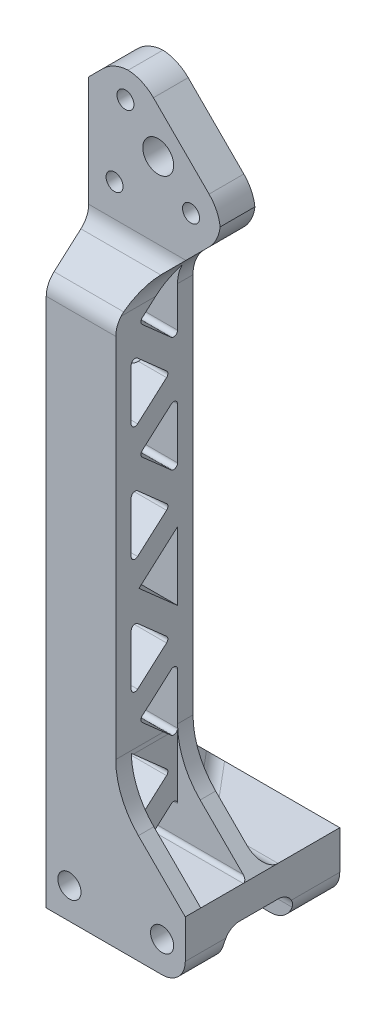
SolidWorks part; units mm, degrees
ref_plane "Front Plane" through (0, 0, 0) normal (0, 0, 1) x (1, 0, 0)
ref_plane "Top Plane" through (0, 0, 0) normal (0, 1, 0) x (1, 0, 0)
ref_plane "Right Plane" through (0, 0, 0) normal (1, 0, 0) x (0, 0, -1)
sketch "Sketch1" plane through (0, 0, 0) normal (0, 0, 1) x (1, 0, 0)
  line L0 (0, 90.435) -> (0, 0)
  line L1 (0, 0) -> (15, 0)
  line L2 (18, 3) -> (18, 8)
  line L3 (18, 8) -> (11.9289, 14.0711)
  line L4 (9, 21.1421) -> (9, 72.565)
  line L5 (9, 72.565) -> (9, 86) construction
  line L6 (3, 4) -> (15, 4) construction
  line L7 (0, 90.435) -> (3.3076, 93.7426)
  line L8 (3.3076, 93.7426) -> (6.9142, 93.7426)
  line L9 (6.9142, 93.7426) -> (17.0459, 83.6109)
  line L10 (17.0459, 83.6109) -> (17.0459, 80.6109)
  line L11 (17.0459, 80.6109) -> (9, 72.565)
  line L12 (4.7574, 90.2426) -> (9, 86) construction
  line L13 (9, 86) -> (13.2426, 81.7574) construction
  line L14 (9, 86) -> (3.3431, 80.3431) construction
  circle A0 centre (9, 86) radius 6 construction
  circle A1 centre (9, 86) radius 8 construction
  circle A2 centre (15, 4) radius 1.5
  circle A3 centre (3, 4) radius 1.5
  arc A4 (15, 0) -> (18, 3) centre (15, 3) ccw
  circle A5 centre (13.2426, 81.7574) radius 1.1
  circle A6 centre (3.3431, 80.3431) radius 1.1
  circle A7 centre (4.7574, 90.2426) radius 1.1
  circle A8 centre (9, 86) radius 2
  arc A9 (11.9289, 14.0711) -> (9, 21.1421) centre (19, 21.1421) cw
  point P16 (18, 0)
  point P30 (3.3431, 93.7426)
  point P31 (0, 90.2426)
  point P32 (17.0459, 83.6109)
  dimension "D7" = 3
  dimension "D8" = 3
  dimension "D11" = 12
  dimension "D12" = 16
  dimension "D17" = 2.2
  dimension "D21" = 4
  dimension "D24" = 10
  dimension "D1" = 18
  dimension "D2" = 8
  dimension "D3" = 12
  dimension "D4" = 4
  dimension "D5" = 3
  dimension "D6" = 135
  dimension "D9" = 9
  dimension "D10" = 82
  dimension "D13" = 45
  dimension "D14" = 90
  dimension "D15" = 90
  dimension "D16" = 3.5
  dimension "D18" = 3.5
  dimension "D19" = 3.5
  dimension "D20" = 45
  dimension "D22" = 4
  dimension "D23" = 3
extrude "Boss-Extrude1" add sketch "Sketch1" along normal mid plane 10
sketch "Sketch2" plane through (0, 0, 0) normal (-1, 0, 0) x (0, 0, 1)
  line L0 (-3, -952.5072) -> (-3, 49047.4928) construction
  line L1 (-2, -952.5072) -> (-2, 49047.4928) construction
  line L2 (3, 8) -> (-3, 8)
  line L3 (0, -952.5072) -> (0, 49047.4928) construction
  line L4 (2, -952.5072) -> (2, 49047.4928) construction
  line L5 (3, -952.2832) -> (3, 49047.7168) construction
  line L6 (5, 90.435) -> (5, 0) construction
  line L7 (-5, 90.435) -> (-5, 0) construction
  line L8 (-3, 8) -> (-3, 13.3)
  line L9 (-3, 13.3) -> (3, 8)
  line L10 (3, 12.0028) -> (-2, 16.4195)
  line L11 (-2, 16.4195) -> (3, 20.8361)
  line L12 (3, 20.8361) -> (3, 12.0028)
  line L13 (2, 23.9556) -> (-3, 28.3723)
  line L14 (-3, 28.3723) -> (-3, 19.539)
  line L15 (-3, 19.539) -> (2, 23.9556)
  line L16 (3, 35.7111) -> (3, 26.8778)
  line L17 (3, 26.8778) -> (-2, 31.2944)
  line L18 (-2, 31.2944) -> (3, 35.7111)
  line L19 (-3, 34.4139) -> (2, 38.8306)
  line L20 (2, 38.8306) -> (-3, 43.2473)
  line L21 (-3, 43.2473) -> (-3, 34.4139)
  line L22 (3, 50.5861) -> (3, 41.7527)
  line L23 (3, 41.7527) -> (-2, 46.1694)
  line L24 (-2, 46.1694) -> (3, 50.5861)
  line L25 (-3, 49.2889) -> (2, 53.7056)
  line L26 (2, 53.7056) -> (-3, 58.1222)
  line L27 (-3, 58.1222) -> (-3, 49.2889)
  line L28 (3, 65.461) -> (3, 56.6277)
  line L29 (3, 56.6277) -> (-2, 61.0444)
  line L30 (-2, 61.0444) -> (3, 65.461)
  line L31 (-3, 64.1639) -> (2, 68.5805)
  line L32 (2, 68.5805) -> (-3, 72.9972)
  line L33 (-3, 72.9972) -> (-3, 64.1639)
  line L34 (3, 77) -> (-3, 77)
  line L35 (-3, 77) -> (3, 71.7)
  line L36 (3, 71.7) -> (3, 77)
  line L37 (5, 0) -> (-5, 0) construction
  point P46 (3, 77.7156)
  dimension "D1" = 2
  dimension "D2" = 2
  dimension "D3" = 1
  dimension "D4" = 1
  dimension "D5" = 2
  dimension "D6" = 5.3
  dimension "D7" = 3
  dimension "D8" = 3
  dimension "D10" = 8
  dimension "D11" = 77
  dimension "D12" = 3
  dimension "D9" = 4
extrude "Cut-Extrude1" cut sketch "Sketch2" against normal up to next
sketch "Sketch4" plane through (9, 0, 0) normal (1, 0, 0) x (0, 0, -1)
  line L0 (3, 13.3) -> (-3, 8) construction
  line L1 (-3, 20.6146) -> (3, 20.6146)
  line L2 (-3, 20.6146) -> (-3, 8)
  line L3 (-3, 8) -> (3, 8)
  line L4 (3, 20.6146) -> (3, 8)
  line L5 (-3, 8) -> (3, 8) construction
  line L6 (3, 8) -> (3, 13.3) construction
  point P5 (17.0564, 11.8928)
  point P6 (15.2929, 42.4359)
  point P7 (-2.6159, 8.3393)
  point P10 (-1.8825, 8.9872)
  point P11 (3, 8)
  point P16 (-3, 8)
  point P17 (-3, 20.6146)
extrude "Cut-Extrude3" cut sketch "Sketch4" along normal up to next
fillet "Fillet1" radius 0.5 24 edges at (4.5, 13.3, -3) (9, 8, -3) (4.5, 12.0028, 3) (4.5, 16.4195, -2) (4.5, 19.539, -3) (4.5, 28.3723, -3) (4.5, 23.9556, 2) (4.5, 26.8778, 3) (4.5, 31.2944, -2) (4.5, 35.7111, 3) (4.5, 50.5861, 3) (4.5, 46.1694, -2) (4.5, 41.7527, 3) (4.5, 58.1222, -3) (4.5, 49.2889, -3) (4.5, 53.7056, 2) (4.5, 56.6277, 3) (4.5, 65.461, 3) (4.5, 61.0444, -2) (4.5, 64.1639, -3) (4.5, 68.5805, 2) (6.7175, 77, -3) (4.5, 71.7, 3) (6.7175, 77, 3)
sketch "Sketch5" plane through (0, 0, -5) normal (0, 0, -1) x (-1, 0, 0)
  line L0 (-18, 8) -> (0, 8)
  line L1 (0, 90.435) -> (0, 0) construction
  line L2 (-18, 3) -> (-18, 8) construction
  line L3 (0, 0) -> (-15, 0) construction
  line L4 (0, 90.435) -> (0, 0)
  line L5 (-18, 3) -> (-18, 8)
  line L6 (0, 0) -> (-15, 0)
  circle A0 centre (-3, 4) radius 1.5 construction
  arc A1 (-18, 3) -> (-15, 0) centre (-15, 3) ccw construction
  circle A2 centre (-3, 4) radius 1.5
  arc A3 (-18, 3) -> (-15, 0) centre (-15, 3) ccw
  circle A4 centre (-15, 4) radius 1.5 construction
  circle A5 centre (-15, 4) radius 1.5
  circle M4 centre (-15, 4) radius 1.5
  line M13 (-18, 8) -> (-18, 3)
  arc M14 (-18, 3) -> (-15, 0) centre (-15, 3) ccw
  line M15 (-15, 0) -> (0, 0)
  line M16 (0, 0) -> (0, 90.435)
  circle M17 centre (-3, 4) radius 1.5
extrude "Boss-Extrude2" add sketch "Sketch5" along normal blind 10 contours L0 M13 M14 M15 M16 M17 M4 region at (8.8742, 4.0503, -5)
sketch "Sketch6" plane through (0, 0, 0) normal (-1, 0, 0) x (0, 0, 1)
  line L0 (5, 0) -> (-15, 0) construction
  line L1 (-9, 0) -> (0, 0)
  line L2 (-9, 0) -> (-9, 4)
  line L3 (-9, 4) -> (0, 4)
  line L4 (0, 0) -> (0, 4)
  line L5 (5, 90.435) -> (5, 0) construction
  line L6 (-15, 0) -> (-15, 8) construction
  dimension "D1" = 4
  dimension "D2" = 5
  dimension "D3" = 6
extrude "Cut-Extrude4" cut sketch "Sketch6" against normal through all
sketch "Sketch7" plane through (0, 0, 0) normal (-1, 0, 0) x (0, 0, 1)
  line L0 (3, 72.8088) -> (3, 76.5) construction
  line L1 (-2.0097, 76.1253) -> (2.169, 72.4341) construction
  line L2 (2.5, 77) -> (-1.6787, 77) construction
  line L3 (3, 72.8088) -> (3, 76.5)
  line L4 (-2.0097, 76.1253) -> (2.169, 72.4341)
  line L5 (2.5, 77) -> (-1.6787, 77)
  arc A0 (3, 76.5) -> (2.5, 77) centre (2.5, 76.5) ccw construction
  arc A1 (2.169, 72.4341) -> (3, 72.8088) centre (2.5, 72.8088) ccw construction
  arc A2 (-1.6787, 77) -> (-2.0097, 76.1253) centre (-1.6787, 76.5) ccw construction
  arc A3 (3, 76.5) -> (2.5, 77) centre (2.5, 76.5) ccw
  arc A4 (2.169, 72.4341) -> (3, 72.8088) centre (2.5, 72.8088) ccw
  arc A5 (-1.6787, 77) -> (-2.0097, 76.1253) centre (-1.6787, 76.5) ccw
extrude "Boss-Extrude3" add sketch "Sketch7" against normal up to surface (9.2438 mm away) contours L5 A5 L4 A4 L3 A3 up to face at (11.3819, 74.9469, 0.0768)
sketch "Sketch8" plane through (0, 0, 0) normal (-1, 0, 0) x (0, 0, 1)
  line L0 (5, 69.9333) -> (-0.5, 74.7917)
  line L1 (5, 90.435) -> (5, 0) construction
  line L2 (-0.5, 74.7917) -> (-0.5, 97.1757)
  line L3 (-0.5, 97.1757) -> (5, 97.1757)
  line L4 (5, 97.1757) -> (5, 69.9333)
  line L5 (1.5758, 68.9553) -> (-3, 72.9972) construction
  line L7 (-5, 90.435) -> (-5, 8) construction
  dimension "D1" = 3
  dimension "D2" = 4.5
extrude "Cut-Extrude5" cut sketch "Sketch8" against normal through all
sketch "Sketch9" plane through (0, 0, 0) normal (-1, 0, 0) x (0, 0, 1)
  line L0 (-15, 8) -> (-5, 18)
  line L1 (-5, 90.435) -> (-5, 8) construction
  line L2 (-5, 18) -> (-5, 8)
  line L3 (-15, 8) -> (-5, 8) construction
  line L4 (-5, 8) -> (-15, 8)
  dimension "D1" = 45
extrude "Boss-Extrude4" add sketch "Sketch9" against normal blind 10
fillet "Fillet2" radius 2 2 edges at (9, 4, 0) (9, 4, -9)
chamfer "Chamfer1" distance 7 angle 50 1 edges at (10, 13, -10) first distance on face at (10, 12.6958, -7.5)
fillet "Fillet3" radius 2 3 edges at (5.8289, 13.0503, -5) (5.8289, 8, -10.0503) (14, 8, -5)
fillet "Fillet4" radius 3 2 edges at (5.6133, 74.7917, -0.5) (4.5, 69.9333, 5)
fillet "Fillet5" radius 5 5 edges at (17.0459, 80.6109, -2.75) (17.0459, 83.6109, -2.75) (6.9142, 93.7426, -2.75) (3.3076, 93.7426, -2.75) (9, 72.565, -0.245)
sketch "Sketch10" plane through (0, 0, -5) normal (0, 0, -1) x (-1, 0, 0)
  line L0 (0, 90.435) -> (0, 18) construction
  circle A0 centre (-4.5, 61.5855) radius 1.25
  point P2 (0, 0)
  point P3 (0, 0)
  dimension "D3" = 2.5
  dimension "D1" = 4.5
  dimension "D2" = 32.15
extrude "Cut-Extrude6" cut sketch "Sketch10" against normal blind 6
